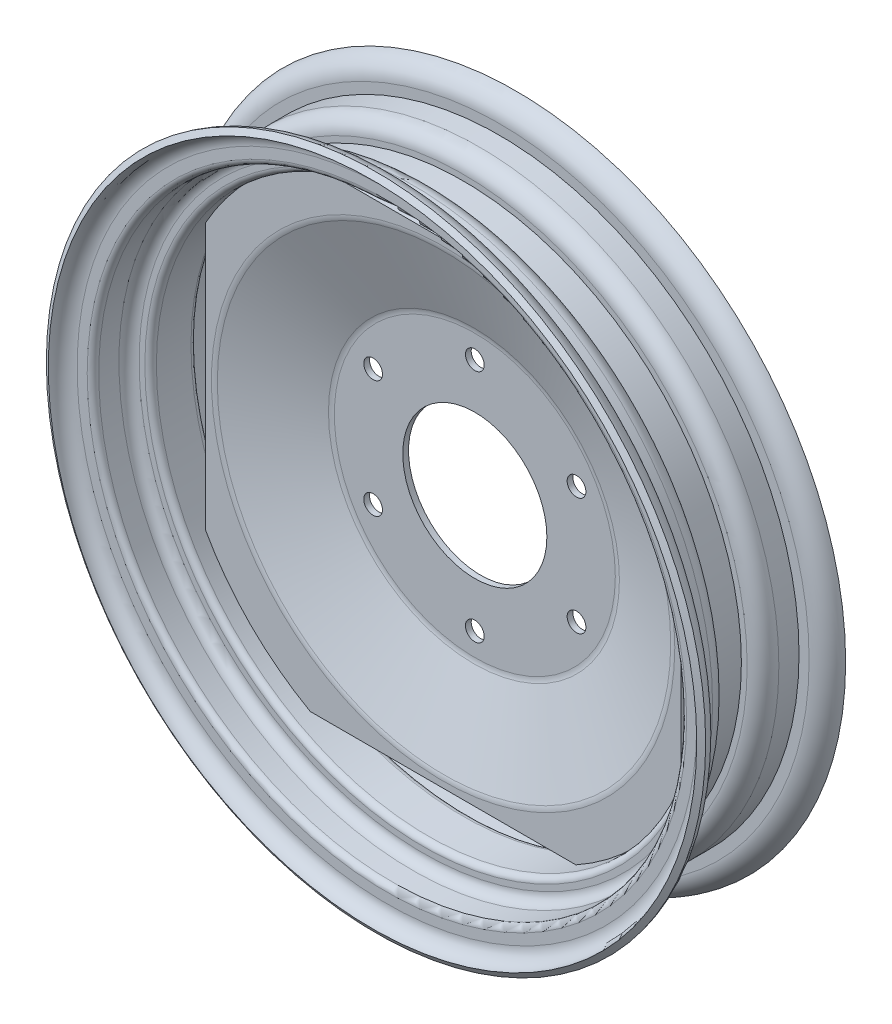
SolidWorks part; units mm, degrees
ref_plane "Front Plane" through (0, 0, 0) normal (0, 0, 1) x (1, 0, 0)
ref_plane "Top Plane" through (0, 0, 0) normal (0, 1, 0) x (1, 0, 0)
ref_plane "Right Plane" through (0, 0, 0) normal (1, 0, 0) x (0, 0, -1)
sketch "Sketch2" plane through (0, 0, 0) normal (1, 0, 0) x (0, 0, -1)
  line L0 (-2, 189) -> (-2, 160.7835)
  line L1 (-1.3834, 157.3264) -> (19.3834, 100.9602)
  line L2 (0, 0) -> (0, 189) construction
  line L3 (51, 225) -> (48.57, 228.7875)
  line L4 (37, 215) -> (37, 208)
  line L5 (37, 208) -> (23, 208)
  line L6 (12, 197) -> (12, 193)
  line L7 (12, 193) -> (-12, 193)
  line L8 (-12, 193) -> (-12, 197)
  line L9 (-23, 208) -> (-37, 208)
  line L10 (-41, 208) -> (-41, 215)
  line L11 (-23, 204) -> (-37, 204)
  line L12 (-16, 193) -> (-16, 197)
  line L13 (12, 189) -> (-12, 189)
  line L14 (16, 197) -> (16, 193)
  line L15 (37, 204) -> (23, 204)
  line L16 (41, 215) -> (41, 208)
  line L17 (20, 97.5031) -> (20, 50)
  line L18 (20, 50) -> (24, 50)
  line L19 (24, 50) -> (24, 98.2165)
  line L20 (-37, 208) -> (-37, 215)
  line L21 (-48.57, 228.7875) -> (-51, 225)
  line L22 (23.3834, 101.6736) -> (2.6166, 158.0398)
  line L23 (-48.57, 228.7875) -> (-53, 221.8827) construction
  line L24 (53, 221.8827) -> (48.57, 228.7875) construction
  line L25 (2, 161.4969) -> (2, 189)
  line L26 (-23, 204) -> (-41, 204) construction
  line L27 (-41, 204) -> (-41, 215) construction
  line L29 (16, 189) -> (-16, 189) construction
  line L30 (-63.5353, 0) -> (63.5353, 0) construction
  line L31 (-51, 225) -> (51, 225) construction
  line L32 (0, 225) -> (0, 189) construction
  line L33 (-16, 189) -> (-16, 197) construction
  line L34 (16, 197) -> (16, 189) construction
  line L35 (41, 204) -> (23, 204) construction
  line L36 (41, 215) -> (41, 204) construction
  line L84 (-46.8315, 224.0898) -> (-49, 220.7099) construction
  line L85 (-49, 220.7099) -> (-49, 0) construction
  line L86 (-53, 221.8827) -> (-53, 0) construction
  line L87 (49, 220.7099) -> (49, 0) construction
  line L88 (49, 220.7099) -> (46.8315, 224.0898) construction
  line L89 (53, 221.8827) -> (53, 0) construction
  arc A0 (48.57, 228.7875) -> (37, 215) centre (51, 215) ccw
  arc A1 (23, 208) -> (12, 197) centre (23, 197) ccw
  arc A2 (-12, 197) -> (-23, 208) centre (-23, 197) ccw
  arc A3 (-37, 215) -> (-48.57, 228.7875) centre (-51, 215) ccw
  arc A4 (-41, 215) -> (-51, 225) centre (-51, 215) ccw
  arc A5 (-16, 197) -> (-23, 204) centre (-23, 197) ccw
  arc A6 (23, 204) -> (16, 197) centre (23, 197) ccw
  arc A7 (51, 225) -> (41, 215) centre (51, 215) ccw
  arc A8 (-41, 215) -> (-46.8315, 224.0898) centre (-51, 215) ccw construction
  arc A9 (46.8315, 224.0898) -> (41, 215) centre (51, 215) ccw construction
  arc A10 (-2, 160.7835) -> (-1.3834, 157.3264) centre (8, 160.7835) ccw
  arc A11 (2.6166, 158.0398) -> (2, 161.4969) centre (12, 161.4969) cw
  arc A12 (24, 98.2165) -> (23.3834, 101.6736) centre (14, 98.2165) ccw
  arc A13 (19.3834, 100.9602) -> (20, 97.5031) centre (10, 97.5031) cw
  arc A14 (-37, 204) -> (-41, 208) centre (-37, 208) cw
  arc A15 (-12, 189) -> (-16, 193) centre (-12, 193) cw
  arc A16 (12, 189) -> (16, 193) centre (12, 193) ccw
  arc A17 (37, 204) -> (41, 208) centre (37, 208) ccw
  point P28 (-41, 204)
  point P33 (-16, 189)
  point P122 (-2, 159)
  point P127 (24, 100)
  dimension "D2" = 7
  dimension "D3" = 10
  dimension "D11" = 11
  dimension "D20" = 10
  dimension "D8" = 4
  dimension "D4" = 4
  dimension "D5" = 20
  dimension "D6" = 2
  dimension "D7" = 50
  dimension "D9" = 15
  dimension "D10" = 50
  dimension "D12" = 4
  dimension "D13" = 30
  dimension "D14" = 189
  dimension "D15" = 4
  dimension "D16" = 2
  dimension "D17" = 36
  dimension "D18" = 102
  dimension "D19" = 4.5
  dimension "D21" = 24
revolve "Revolve1" add sketch "Sketch2" angle 360 about L30 region at (0, 119.7745, -12.5393) region at (0, 190.0949, 7)
sketch "Sketch6" plane through (0, 0, 0) normal (0, 0, 1) x (1, 0, 0)
  line L0 (0, 0) -> (-165, 0) construction
  line L1 (92.1737, 165) -> (-92.1737, 165)
  line L2 (165, -92.1737) -> (165, 92.1737)
  line L3 (-92.1737, -165) -> (92.1737, -165)
  line L5 (-165, 92.1737) -> (-165, -92.1737)
  circle A0 centre (0, 0) radius 189 construction
  arc A1 (92.1737, 165) -> (-92.1737, 165) centre (0, 0) ccw
  arc A2 (-165, 92.1737) -> (-165, -92.1737) centre (0, 0) ccw
  arc A3 (-92.1737, -165) -> (92.1737, -165) centre (0, 0) ccw
  arc A4 (165, -92.1737) -> (165, 92.1737) centre (0, 0) ccw
  dimension "D1" = 165
  dimension "D2" = 4
extrude "Cut-Extrude1" cut sketch "Sketch6" along normal up to next and the other way up to next
hole_wizard "Ø13.0 (13) Diameter Hole1" positions "Sketch8" profile "Sketch7" hole size "Ø13.0" standard "Ansi Metric"
sketch "Sketch8" plane through (0, 0, -20) normal (0, 0, 1) x (1, 0, 0)
  line L4 (0, 50) -> (0, 97.5031) construction
  line L6 (0, -50) -> (0, -97.5031) construction
  circle A1 centre (0, 0) radius 50 construction
  circle A2 centre (0, 0) radius 97.5031 construction
  point P0 (0, 81.5)
  point P20 (70.5811, 40.75)
  point P21 (70.5811, -40.75)
  point P22 (0, -81.5)
  point P23 (-70.5811, -40.75)
  point P24 (-70.5811, 40.75)
  dimension "D2" = 81.5
  dimension "D3" = 81.5
  dimension "D1" = 6
sketch "Sketch7" plane through (0, 81.5, -20) normal (1, 0, 0) x (0, -1, 0)
  line L0 (0, 0) -> (0, 30)
  line L1 (0, 30) -> (6.5, 30)
  line L2 (6.5, 30) -> (6.5, 0)
  line L5 (6.5, 0) -> (0, 0)
  line L10 (0, 30) -> (-6.5, 30) construction
  line L11 (0, -6.35) -> (0, 107.95) construction
  dimension "Hole Dia." = 13
  dimension "Hole Depth" = 30
  dimension "Drill Angle" = 180
